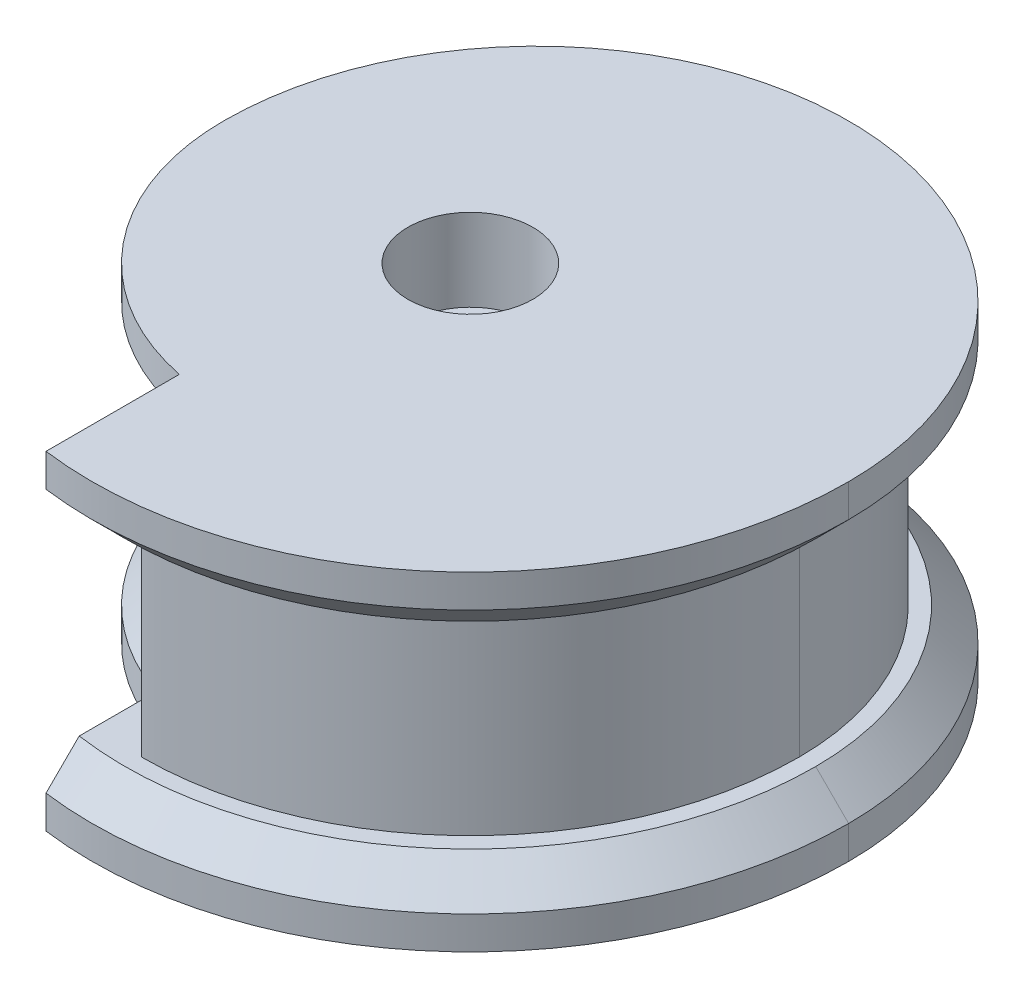
SolidWorks part; units mm, degrees
ref_plane "Front Plane" through (0, 0, 0) normal (0, 0, 1) x (1, 0, 0)
ref_plane "Top Plane" through (0, 0, 0) normal (0, 1, 0) x (1, 0, 0)
ref_plane "Right Plane" through (0, 0, 0) normal (1, 0, 0) x (0, 0, -1)
sketch "Sketch1" plane through (0, 0, 0) normal (0, 1, 0) x (1, 0, 0)
  circle A0 centre (0, 0) radius 6
  dimension "D1" = 12
extrude "Boss-Extrude1" add sketch "Sketch1" along normal blind 10
sketch "Sketch2" plane through (0, 10, 0) normal (0, 1, 0) x (1, 0, 0)
  circle A0 centre (0, 0) radius 1.9
  dimension "D1" = 3.8
extrude "Cut-Extrude1" cut sketch "Sketch2" against normal blind 2.5
sketch "Sketch3" plane through (0, 0, 0) normal (0, -1, 0) x (1, 0, 0)
  circle A0 centre (0, 0) radius 3.75
  dimension "D1" = 7.5
extrude "Cut-Extrude2" cut sketch "Sketch3" against normal blind 4.8
sketch "Sketch5" plane through (0, 0, 0) normal (0, -1, 0) x (1, 0, 0)
  line L2 (0, 6) -> (0, 10)
  circle A1 centre (0, 0) radius 6 construction
  arc A2 (-6, 0) -> (10, 0) centre (2, 0) ccw
  arc A4 (10, 0) -> (0, 10) centre (0, 0) ccw
  arc A5 (-6, 0) -> (0, 6) centre (0, 0) ccw
extrude "Boss-Extrude2" add sketch "Sketch5" against normal up to surface (10 mm away) up to face at (0, 10, 1.9)
sketch "Sketch7" plane through (0, 0, 0) normal (0, -1, 0) x (1, 0, 0)
  line L0 (0, 10) -> (0, 6)
  line L1 (-1.5, 11.4018) -> (-1.5, 7.3485)
  arc A0 (10, 0) -> (0, 10) centre (0, 0) ccw
  arc A1 (-6, 0) -> (10, 0) centre (2, 0) ccw
  arc A2 (0, 6) -> (-6, 0) centre (0, 0) ccw
  arc A3 (-1.5, 7.3485) -> (-7.5, 0) centre (0, 0) ccw
  arc A4 (-7.5, 0) -> (11.5, 0) centre (2, 0) ccw
  arc A5 (11.5, 0) -> (-1.5, 11.4018) centre (0, 0) ccw
  dimension "D1" = 1.5
extrude "Boss-Extrude3" add sketch "Sketch7" against normal blind 2
sketch "Sketch9" plane through (0, 10, 0) normal (0, 1, 0) x (1, 0, 0)
  line L0 (-1.5, -11.4018) -> (-1.5, -7.3485)
  arc A0 (-1.5, -11.4018) -> (11.5, 0) centre (0, 0) ccw
  arc A1 (11.5, 0) -> (-7.5, 0) centre (2, 0) ccw
  arc A2 (-7.5, 0) -> (-1.5, -7.3485) centre (0, 0) ccw
  circle A3 centre (0, 0) radius 1.9
extrude "Boss-Extrude5" add sketch "Sketch9" against normal blind 2
chamfer "Chamfer1" distance 1 angle 45 6 edges at (-5.8095, 2, 4.7434) (2, 2, -9.5) (7.5829, 2, 8.6458) (-5.8095, 8, 4.7434) (2, 8, -9.5) (7.5829, 8, 8.6458)
